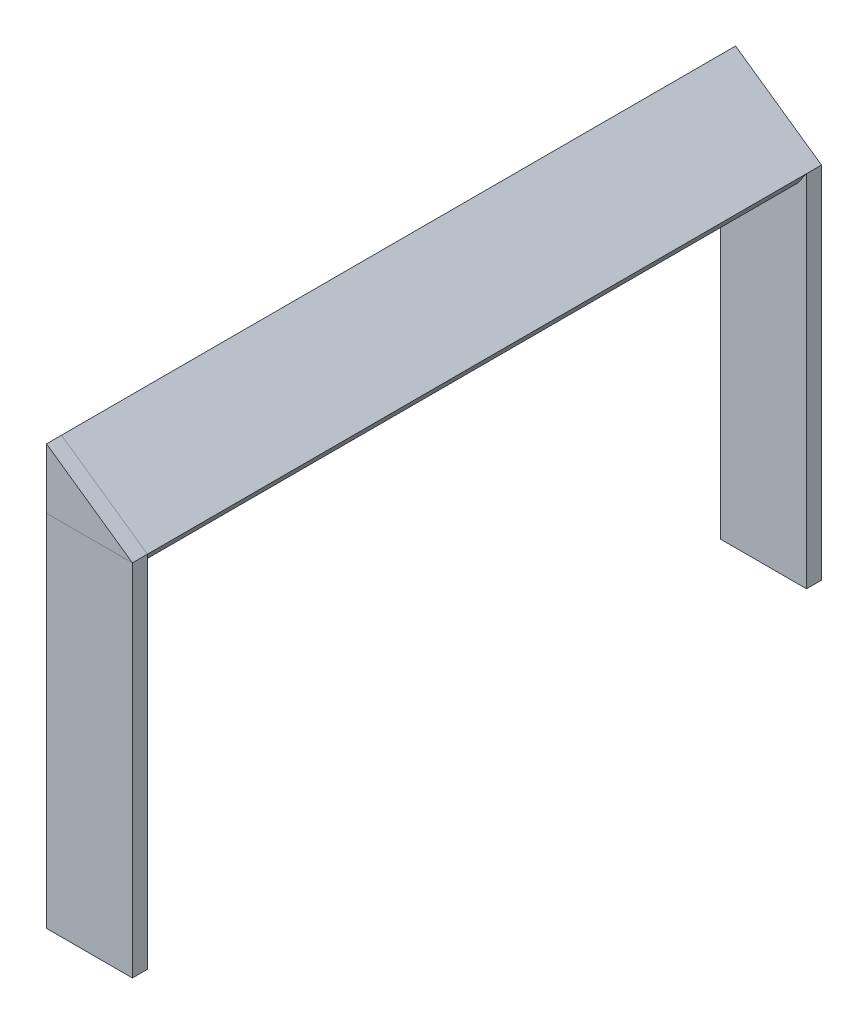
SolidWorks part; units mm, degrees
material "Beech"
ref_plane "Front Plane" through (0, 0, 0) normal (0, 0, 1) x (1, 0, 0)
ref_plane "Top Plane" through (0, 0, 0) normal (0, 1, 0) x (1, 0, 0)
ref_plane "Right Plane" through (0, 0, 0) normal (1, 0, 0) x (0, 0, -1)
sketch "Sketch1" plane through (0, 0, 0) normal (0, 0, 1) x (1, 0, 0)
  line L0 (-18.2057, 25.4955) -> (18.2057, 0)
  line L1 (18.2057, 0) -> (-18.2057, 0)
  line L2 (-18.2057, 0) -> (-18.2057, 25.4955)
  point P2 (0, 0)
  dimension "D1" = 44.45
  dimension "D2" = 55
extrude "Boss-Extrude1" add sketch "Sketch1" along normal blind 6.35
sketch "Sketch2" plane through (0, 0, 0) normal (0, 0, 1) x (1, 0, 0)
  line L1 (-18.2057, 0) -> (18.2057, 0) construction
  line L2 (-18.2057, 0) -> (18.2057, 0)
  line L3 (-18.2057, 0) -> (-18.2057, -152.4)
  line L4 (-18.2057, -152.4) -> (18.2057, -152.4)
  line L5 (18.2057, 0) -> (18.2057, -152.4)
  dimension "D1" = 152.4
extrude "Boss-Extrude2" add sketch "Sketch2" along normal blind 6.35 separate body
sketch "Sketch3" plane through (0, 0, 0) normal (0, 0, 1) x (1, 0, 0)
  line L0 (-18.2057, 25.4955) -> (18.2057, 0)
  line L1 (-18.2057, 25.4955) -> (-21.8479, 20.2939)
  line L2 (18.2057, 0) -> (14.5634, -5.2016)
  line L3 (-21.8479, 20.2939) -> (14.5634, -5.2016)
  dimension "D1" = 6.35
extrude "Boss-Extrude3" add sketch "Sketch3" against normal blind 279.4 separate body
ref_plane "Plan1" through (0, 0, -139.7) normal (0, 0, 1) x (1, 0, 0)
mirror "Symétrie2" about plane through (0, 0, -139.7) normal (0, 0, 1) of "Boss-Extrude2", "Boss-Extrude1"
